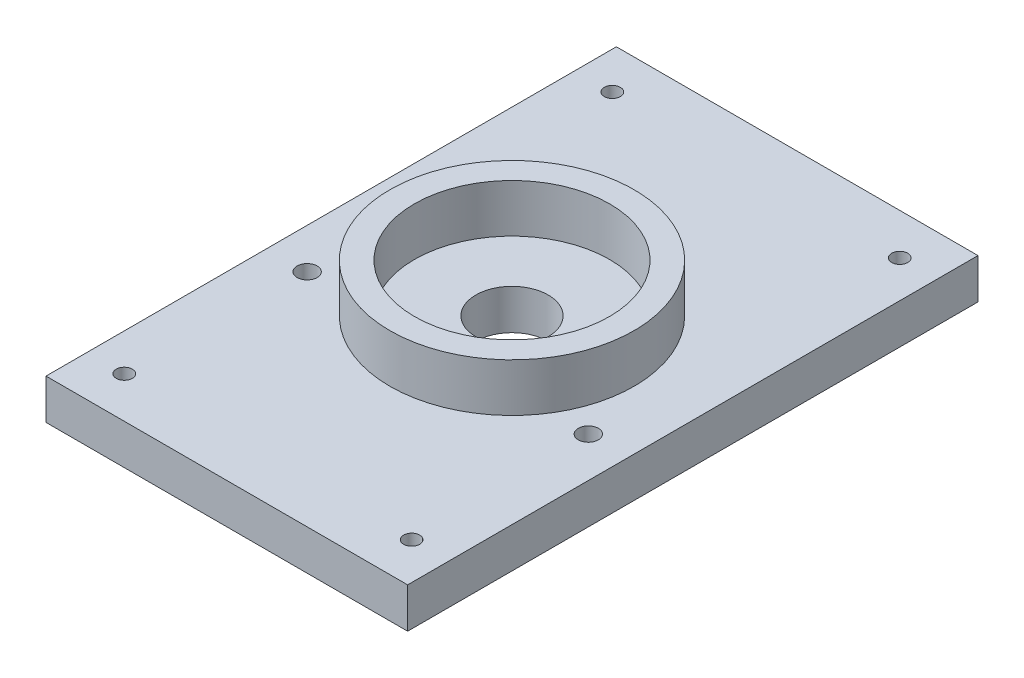
SolidWorks part; units mm, degrees
ref_plane "Front Plane" through (0, 0, 0) normal (0, 0, 1) x (1, 0, 0)
ref_plane "Top Plane" through (0, 0, 0) normal (0, 1, 0) x (1, 0, 0)
ref_plane "Right Plane" through (0, 0, 0) normal (1, 0, 0) x (0, 0, -1)
sketch "Sketch1" plane through (0, 0, 0) normal (0, 1, 0) x (1, 0, 0)
  line L0 (-22.3715, -35.0908) -> (22.6443, -35.0908)
  line L1 (22.6443, -35.0908) -> (22.6443, 35.9092)
  line L2 (22.6443, 35.9092) -> (-22.3715, 35.9092)
  line L3 (-22.3715, 35.9092) -> (-22.3715, -35.0908)
  circle A0 centre (17.6364, -7.5908) radius 1.75
  circle A1 centre (0.1364, 0.4092) radius 4.5
  circle A2 centre (-17.3636, -7.5908) radius 1.75
extrude "Boss-Extrude1" add sketch "Sketch1" along normal blind 5
sketch "Sketch2" plane through (0, 5, 0) normal (0, 1, 0) x (1, 0, 0)
  circle A0 centre (0.1364, 0.4092) radius 12.2
  circle A1 centre (0.1364, 0.4092) radius 15.2
  dimension "D1" = 24.4
  dimension "D2" = 3
extrude "Boss-Extrude2" add sketch "Sketch2" along normal blind 6
sketch "Sketch3" plane through (0, 0, 0) normal (0, -1, 0) x (1, 0, 0)
  line L0 (22.6443, 35.0908) -> (-22.3715, 35.0908)
  line L2 (-22.3715, -35.9092) -> (22.6443, -35.9092)
  circle A0 centre (18.0229, -30.7879) radius 1.5
  circle A1 centre (-17.7501, -30.7879) radius 1.5
  circle A2 centre (-17.7501, 29.9695) radius 1.5
  circle A3 centre (18.0229, 29.9695) radius 1.5
  point P0 (-22.3715, -35.9092)
extrude "Cut-Extrude1" cut sketch "Sketch3" against normal blind 60 contours A3 | A2 | A1 | A0 region at (18.0229, 0, -30.7879) region at (-17.7501, 0, -30.7879) region at (-17.7501, 0, 29.9695) region at (18.0229, 0, 29.9695)
sketch "Sketch4" plane through (0, 11, 0) normal (0, 1, 0) x (1, 0, 0)
  circle A0 centre (0.1364, 0.4092) radius 4.5 construction
  circle A1 centre (0.1364, 0.4092) radius 4.5
  circle A2 centre (0.1364, 0.4092) radius 12.15
  circle A4 centre (0.1364, 0.4092) radius 12.2 construction
  circle A5 centre (0.1364, 0.4092) radius 12.2
  circle M2 centre (0.1364, 0.4092) radius 12.2
  dimension "D1" = 24.3
extrude "Boss-Extrude3" add sketch "Sketch4" against normal up to surface (6 mm away) contours A2 M2 region at (-12.0291, 11, -0.4092) up to face at (0.1364, 5, 4.0908)
sketch "Sketch5" plane through (0, 5, 0) normal (0, 1, 0) x (1, 0, 0)
  circle A0 centre (-17.7501, -29.9695) radius 1.5 construction
  circle A1 centre (18.0229, -29.9695) radius 1.5 construction
  circle A2 centre (17.6364, -7.5908) radius 1.75 construction
  circle A3 centre (-17.3636, -7.5908) radius 1.75 construction
  circle A4 centre (-17.7501, 30.7879) radius 1.5 construction
  circle A5 centre (18.0229, 30.7879) radius 1.5 construction
  circle A6 centre (-17.7501, -29.9695) radius 1.5
  circle A7 centre (18.0229, -29.9695) radius 1.5
  circle A8 centre (17.6364, -7.5908) radius 1.75
  circle A9 centre (-17.3636, -7.5908) radius 1.75
  circle A10 centre (-17.7501, 30.7879) radius 1.5
  circle A11 centre (18.0229, 30.7879) radius 1.5
  circle A12 centre (-17.7501, -29.9695) radius 1
  circle A13 centre (18.0229, -29.9695) radius 1
  circle A14 centre (17.6364, -7.5908) radius 1.25
  circle A15 centre (-17.3636, -7.5908) radius 1.25
  circle A16 centre (-17.7501, 30.7879) radius 1
  circle A17 centre (18.0229, 30.7879) radius 1
  dimension "D1" = 0.5
extrude "Boss-Extrude4" add sketch "Sketch5" against normal up to surface (5 mm away) up to face at (18.0229, 0, -32.2879)
ref_axis "Axis1" through (0.1364, -47.6595, -0.4092) along (0, 1, 0)
